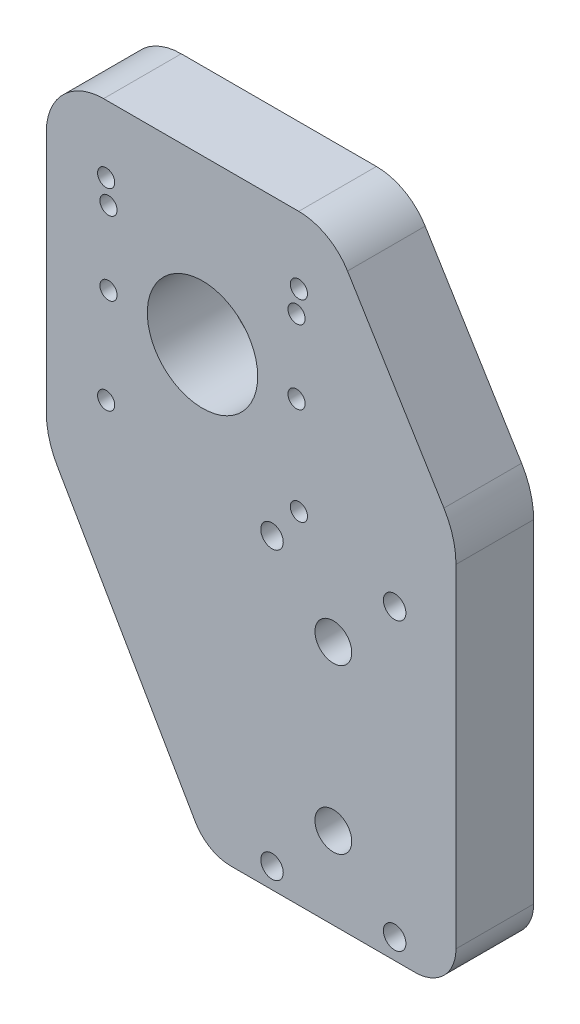
SolidWorks part; units mm, degrees
ref_plane "Front Plane" through (0, 0, 0) normal (0, 0, 1) x (1, 0, 0)
ref_plane "Top Plane" through (0, 0, 0) normal (0, 1, 0) x (1, 0, 0)
ref_plane "Right Plane" through (0, 0, 0) normal (1, 0, 0) x (0, 0, -1)
sketch "Sketch1" plane through (0, 0, 0) normal (0, 0, 1) x (1, 0, 0)
  line L0 (-130, 510) -> (13.8884, 510) construction
  line L1 (-170.2, 540.8246) -> (-129.3094, 470)
  line L2 (-116.2253, 607) -> (-90, 564.2553)
  line L15 (-90, 473) -> (-90, 564.2553)
  line L16 (-90, 473) -> (-90, 547) construction
  line L24 (-170.2, 540.8246) -> (-170.2, 607)
  line L25 (-170.2, 607) -> (-116.2253, 607)
  line L183 (-129.3094, 470) -> (-93, 470)
  arc A1 (-113.8, 602.2) -> (-116.8, 605.2) centre (-116.8, 602.2) ccw construction
  arc A13 (-90, 473) -> (-93, 470) centre (-93, 473) cw
extrude "Boss-Extrude1" add sketch "Sketch1" along normal blind 19
fillet "Fillet1" radius 10 3 edges at (-129.3094, 470, 9.5) (-170.2, 540.8246, 9.5) (-90, 564.2553, 9.5)
sketch "Sketch2" plane through (0, 0, 19) normal (0, 0, 1) x (1, 0, 0)
  circle A0 centre (-142, 577) radius 13.5
  dimension "D1" = 27
extrude "Cut-Extrude1" cut sketch "Sketch2" against normal blind 20
hole_wizard "Tap Drill for M5 Tap1" positions "Sketch5" profile "Sketch6" hole size "M5" standard "ISO" end condition through all
sketch "Sketch5" plane through (0, 0, 0) normal (0, 0, -1) x (-1, 0, 0)
  line L1 (119, 595) -> (119, 577)
  line L2 (119, 595) -> (165, 595)
  line L3 (165, 595) -> (165, 577)
  line L4 (119, 577) -> (165, 577)
  circle A1 centre (119, 595) radius 2.1
  point P2 (119, 595)
  point P4 (119, 577)
  point P6 (165, 577)
  point P8 (165, 595)
  dimension "D1" = 18
  dimension "D2" = 46
  dimension "D3" = 46
  dimension "D4" = 18
sketch "Sketch6" plane through (-119, 595, 0) normal (1, 0, 0) x (0, 1, 0)
  line L0 (0, 0) -> (0, 19)
  line L1 (0, 19) -> (2.1, 19)
  line L2 (2.1, 19) -> (2.1, 0)
  line L5 (2.1, 0) -> (0, 0)
  line L11 (0, -6.35) -> (0, 107.95) construction
  dimension "Thru Hole Dia." = 4.2
  dimension "Thru Hole Depth" = 19
hole_wizard "M5 Clearance Hole1" positions "Sketch7" profile "Sketch8" hole size "M5" standard "ISO" end condition through all
sketch "Sketch7" plane through (0, 0, 19) normal (0, 0, 1) x (1, 0, 0)
  point P0 (-95, 545)
  point P2 (-125, 545)
  point P4 (-125, 475)
  point P6 (-95, 475)
  point P8 (-110, 490)
  point P10 (-110, 530)
sketch "Sketch8" plane through (-95, 545, 19) normal (1, 0, 0) x (0, -1, 0)
  line L0 (0, 0) -> (0, 19)
  line L1 (0, 19) -> (2.75, 19)
  line L2 (2.75, 19) -> (2.75, 0)
  line L5 (2.75, 0) -> (0, 0)
  line L11 (0, -6.35) -> (0, 107.95) construction
  dimension "Thru Hole Dia." = 5.5
  dimension "Thru Hole Depth" = 19
hole_wizard "Tap Drill for M5 Tap2" positions "Sketch9" profile "Sketch10" hole size "M5" standard "ISO" end condition through all
sketch "Sketch9" plane through (0, 0, 19) normal (0, 0, 1) x (1, 0, 0)
  point P0 (-165.57, 553.43)
  point P2 (-165.57, 600.57)
  point P4 (-118.43, 553.43)
  point P6 (-118.43, 600.57)
sketch "Sketch10" plane through (-165.57, 553.43, 19) normal (1, 0, 0) x (0, -1, 0)
  line L0 (0, 0) -> (0, 19)
  line L1 (0, 19) -> (2.1, 19)
  line L2 (2.1, 19) -> (2.1, 0)
  line L5 (2.1, 0) -> (0, 0)
  line L11 (0, -6.35) -> (0, 107.95) construction
  dimension "Thru Hole Dia." = 4.2
  dimension "Thru Hole Depth" = 19
fillet "Fillet2" radius 4 2 edges at (-116.2253, 607, 9.5) (-170.2, 607, 9.5)
sketch "Sketch11" plane through (0, 0, 19) normal (0, 0, 1) x (1, 0, 0)
  line L0 (-82.9528, 571.8912) -> (-106.531, 610.3213)
  line L1 (-118.464, 617) -> (-166.2, 617)
  line L2 (-180.2, 603) -> (-180.2, 543.5041)
  line L3 (-177.5205, 533.5041) -> (-143.7432, 475)
  line L5 (-80, 480) -> (-80, 561.4321)
  line L6 (-91.4764, 566.6616) -> (-115.0546, 605.0918)
  line L7 (-118.464, 607) -> (-166.2, 607)
  line L8 (-170.2, 603) -> (-170.2, 543.5041)
  line L9 (-168.8603, 538.5041) -> (-132.1962, 475)
  line L10 (-123.5359, 470) -> (-93, 470)
  line L11 (-90, 473) -> (-90, 561.4321)
  line L12 (-91.4764, 566.6616) -> (-115.0546, 605.0918)
  line L13 (-118.464, 607) -> (-166.2, 607)
  line L14 (-170.2, 603) -> (-170.2, 543.5041)
  line L15 (-168.8603, 538.5041) -> (-132.1962, 475)
  line L16 (-135.0829, 470) -> (-90, 470)
  line L17 (-90, 473) -> (-90, 561.4321)
  line L18 (-123.5359, 470) -> (-93, 470) construction
  line L19 (-80, 473) -> (-80, 561.4321) construction
  line L20 (-123.5359, 460) -> (-93, 460) construction
  line L21 (-177.5205, 533.5041) -> (-140.8564, 470) construction
  arc A0 (-106.531, 610.3213) -> (-118.464, 617) centre (-118.464, 603) ccw
  arc A1 (-166.2, 617) -> (-180.2, 603) centre (-166.2, 603) ccw
  arc A2 (-180.2, 543.5041) -> (-177.5205, 533.5041) centre (-160.2, 543.5041) ccw
  arc A5 (-80, 561.4321) -> (-82.9528, 571.8912) centre (-100, 561.4321) ccw
  arc A6 (-115.0546, 605.0918) -> (-118.464, 607) centre (-118.464, 603) ccw
  arc A7 (-166.2, 607) -> (-170.2, 603) centre (-166.2, 603) ccw
  arc A8 (-170.2, 543.5041) -> (-168.8603, 538.5041) centre (-160.2, 543.5041) ccw
  arc A9 (-132.1962, 475) -> (-123.5359, 470) centre (-123.5359, 480) ccw
  arc A10 (-93, 470) -> (-90, 473) centre (-93, 473) ccw
  arc A11 (-90, 561.4321) -> (-91.4764, 566.6616) centre (-100, 561.4321) ccw
  arc A12 (-115.0546, 605.0918) -> (-118.464, 607) centre (-118.464, 603) ccw
  arc A13 (-166.2, 607) -> (-170.2, 603) centre (-166.2, 603) ccw
  arc A14 (-170.2, 543.5041) -> (-168.8603, 538.5041) centre (-160.2, 543.5041) ccw
  arc A15 (-132.1962, 475) -> (-123.5359, 470) centre (-123.5359, 480) ccw
  arc A16 (-93, 470) -> (-90, 473) centre (-93, 473) ccw
  arc A17 (-90, 561.4321) -> (-91.4764, 566.6616) centre (-100, 561.4321) ccw
  arc A18 (-93, 460) -> (-80, 473) centre (-93, 473) ccw construction
  arc A19 (-140.8564, 470) -> (-123.5359, 460) centre (-123.5359, 480) ccw construction
  arc A20 (-143.7432, 475) -> (-135.0829, 470) centre (-135.0829, 480) ccw
  arc A21 (-90, 470) -> (-80, 480) centre (-90, 480) ccw
  line M41 (-91.4764, 566.6616) -> (-115.0546, 605.0918)
  arc M42 (-115.0546, 605.0918) -> (-118.464, 607) centre (-118.464, 603) ccw
  line M43 (-118.464, 607) -> (-166.2, 607)
  arc M44 (-166.2, 607) -> (-170.2, 603) centre (-166.2, 603) ccw
  line M45 (-170.2, 603) -> (-170.2, 543.5041)
  arc M46 (-170.2, 543.5041) -> (-168.8603, 538.5041) centre (-160.2, 543.5041) ccw
  line M47 (-168.8603, 538.5041) -> (-132.1962, 475)
  arc M48 (-132.1962, 475) -> (-123.5359, 470) centre (-123.5359, 480) ccw
  arc M50 (-93, 470) -> (-90, 473) centre (-93, 473) ccw
  line M51 (-90, 473) -> (-90, 561.4321)
  arc M52 (-90, 561.4321) -> (-91.4764, 566.6616) centre (-100, 561.4321) ccw
  dimension "D3" = 10
  dimension "D1" = 0
  dimension "D2" = 10
extrude "Boss-Extrude2" add sketch "Sketch11" against normal up to surface (19 mm away) contours L16 A21 L5 A5 L0 A0 L1 A1 L2 A2 L3 A20 M48 M47 M46 M45 M44 M43 M42 M41 M52 M51 M50 region at (-82.4644, 566.3827, 19) up to face at (-122.25, 475, 0)
hole_wizard "M8 Clearance Hole1" positions "3DSketch1" profile "Sketch12" hole size "M8" standard "ISO" end condition through all
sketch3d "3DSketch1"
  line L0 (-110, 490, 0) -> (-110, 490, 19) construction
  line L1 (-110, 530, 0) -> (-110, 530, 19) construction
  point P0 (-110, 490, 0)
  point P4 (-110, 530, 0)
sketch "Sketch12" plane through (-110, 490, 0) normal (1, 0, 0) x (0, 1, 0)
  line L0 (0, 0) -> (0, 19)
  line L1 (0, 19) -> (4.5, 19)
  line L2 (4.5, 19) -> (4.5, 0)
  line L5 (4.5, 0) -> (0, 0)
  line L11 (0, -6.35) -> (0, 107.95) construction
  dimension "Thru Hole Dia." = 9
  dimension "Thru Hole Depth" = 19
